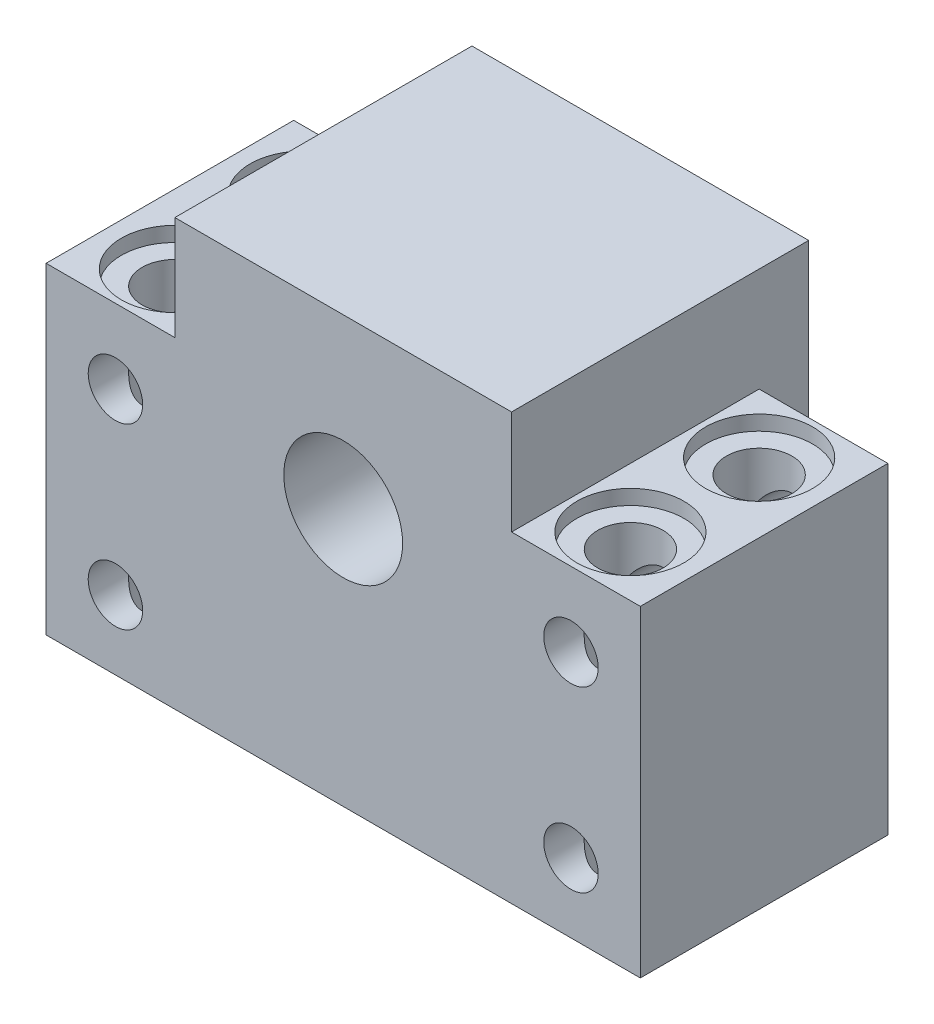
SolidWorks part; units mm, degrees
ref_plane "前视基准面" through (0, 0, 0) normal (0, 0, 1) x (1, 0, 0)
ref_plane "上视基准面" through (0, 0, 0) normal (0, 1, 0) x (1, 0, 0)
ref_plane "右视基准面" through (0, 0, 0) normal (1, 0, 0) x (0, 0, -1)
other "Configuration Table"
sketch "草图1" plane through (0, 0, 0) normal (0, 0, 1) x (1, 0, 0)
  line L0 (0, 0) -> (0, -50000) construction
  line L1 (-30, 16.25) -> (30, 16.25)
  line L2 (-30, 16.25) -> (-30, -16.25)
  line L3 (-30, -16.25) -> (30, -16.25)
  line L4 (30, 16.25) -> (30, -16.25)
  line L5 (-30, 16.25) -> (30, -16.25) construction
  line L6 (-30, -16.25) -> (30, 16.25) construction
  line L7 (-17, 26.75) -> (17, 26.75)
  line L8 (-17, 26.75) -> (-17, 16.25)
  line L9 (-17, 16.25) -> (17, 16.25)
  line L10 (17, 26.75) -> (17, 16.25)
  line L11 (-17, 26.75) -> (17, 16.25) construction
  line L12 (-17, 16.25) -> (17, 26.75) construction
  point P0 (0, 0)
  point P5 (0, 21.5)
  dimension "D1" = 32.5
  dimension "D2" = 60
  dimension "D3" = 43
  dimension "D4" = 34
extrude "凸台-拉伸1" add sketch "草图1" along normal blind 25 contours L4 L1 L2 L3 | L10 L7 L8 L1 region at (0, 0, 0) region at (0, 21.5, 0)
sketch "草图2" plane through (0, 0, 0) normal (0, 0, -1) x (-1, 0, 0)
  line L1 (-17, 26.75) -> (17, 26.75)
  line L2 (-17, 26.75) -> (-17, -7.25)
  line L3 (-17, -7.25) -> (17, -7.25)
  line L4 (17, 26.75) -> (17, -7.25)
  line L5 (-13, 22.75) -> (13, 22.75)
  line L6 (-13, 22.75) -> (-13, -3.25)
  line L7 (-13, -3.25) -> (13, -3.25)
  line L8 (13, 22.75) -> (13, -3.25)
  line L9 (-13, 22.75) -> (13, -3.25) construction
  line L10 (-13, -3.25) -> (13, 22.75) construction
  point P5 (0, 9.75)
  dimension "D1" = 34
  dimension "D2" = 26
  dimension "D3" = 4
  dimension "D4" = 4
extrude "凸台-拉伸2" add sketch "草图2" along normal blind 5
extrude "凸台-拉伸3" add sketch "草图2<2>" along normal blind 9 contours L8 L5 L6 L7 region at (0, 9.75, 0)
sketch "草图2<2>" plane through (0, 0, 0) normal (0, 0, -1) x (-1, 0, 0) same geometry as "草图2"
sketch "草图3" plane through (0, 16.25, 0) normal (0, 1, 0) x (1, 0, 0)
  line L0 (0, 5) -> (0, -49995) construction
  line L1 (-13, 5) -> (13, 5) construction
  line L2 (-30, -25) -> (-30, 0) construction
  line L3 (-30, -12.5) -> (-50030, -12.5) construction
  circle A0 centre (-23, -6) radius 3.3
  circle A1 centre (-23, -19) radius 3.3
  circle A2 centre (23, -6) radius 3.3
  circle A3 centre (23, -19) radius 3.3
  point P4 (0, 5)
  point P15 (-30, -12.5)
  dimension "D1" = 6.6
  dimension "D2" = 7
  dimension "D3" = 13
extrude "切除-拉伸1" cut sketch "草图3" against normal through all
sketch "草图4" plane through (0, 16.25, 0) normal (0, 1, 0) x (1, 0, 0)
  circle A0 centre (-23, -6) radius 5.4
  circle A1 centre (-23, -19) radius 5.4
  circle A2 centre (23, -6) radius 5.4
  circle A3 centre (23, -19) radius 5.4
  dimension "D1" = 10.8
extrude "切除-拉伸2" cut sketch "草图4" against normal blind 1.5
sketch "草图5" plane through (0, 0, 25) normal (0, 0, 1) x (1, 0, 0)
  line L0 (0, 0) -> (0, -50000) construction
  line L1 (30, 16.25) -> (30, -16.25) construction
  line L2 (-30, -16.25) -> (30, -16.25) construction
  line L3 (-17, 26.75) -> (17, 26.75) construction
  circle A0 centre (23, -9.25) radius 2.75
  circle A1 centre (23, 8.75) radius 2.75
  circle A2 centre (-23, 8.75) radius 2.75
  circle A3 centre (-23, -9.25) radius 2.75
  circle A4 centre (0, 9.75) radius 6
  dimension "D1" = 7
  dimension "D2" = 7
  dimension "D3" = 18
  dimension "D4" = 5.5
  dimension "D5" = 17
  dimension "D6" = 12
extrude "切除-拉伸3" cut sketch "草图5" against normal through all
